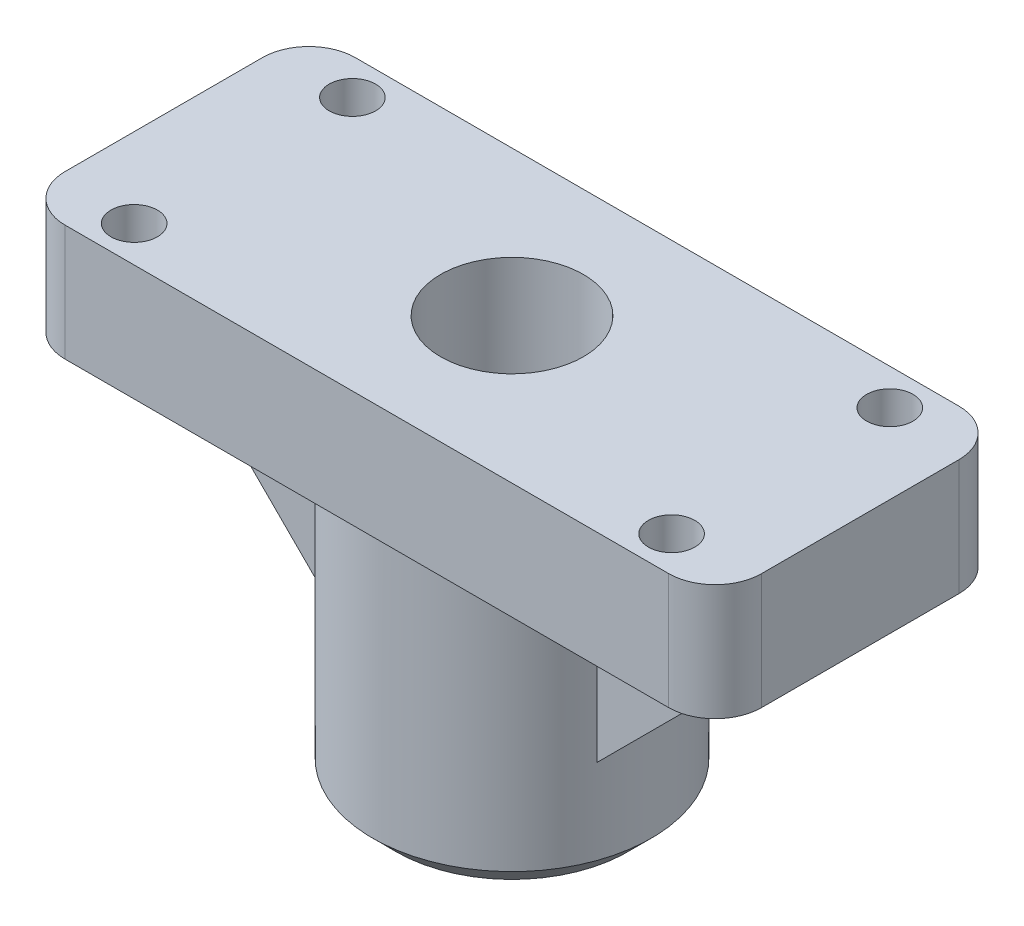
SolidWorks part; units mm, degrees
ref_plane "Front Plane" through (0, 0, 0) normal (0, 0, 1) x (1, 0, 0)
ref_plane "Top Plane" through (0, 0, 0) normal (0, 1, 0) x (1, 0, 0)
ref_plane "Right Plane" through (0, 0, 0) normal (1, 0, 0) x (0, 0, -1)
sketch "Sketch1" plane through (0, 0, 0) normal (0, 1, 0) x (1, 0, 0)
  line L1 (-30, 12.5) -> (30, 12.5)
  line L2 (-30, 12.5) -> (-30, -12.5)
  line L3 (-30, -12.5) -> (30, -12.5)
  line L4 (30, 12.5) -> (30, -12.5)
  point P4 (0, 12.5)
  point P6 (-30, 0)
  dimension "D1" = 25
  dimension "D2" = 60
extrude "Base" add sketch "Sketch1" along normal blind 10
sketch "Sketch2" plane through (0, 0, 0) normal (0, 0, 1) x (1, 0, 0)
  line L0 (0, 0) -> (0, -20.6179) construction
  line L1 (-6.15, 0) -> (-6.15, -7)
  line L2 (-30, 0) -> (30, 0) construction
  line L3 (-6.15, -7) -> (-5.35, -7)
  line L4 (-5.35, -7) -> (-5.35, -25)
  line L5 (-5.35, -25) -> (-12, -25)
  line L6 (-12, -25) -> (-12, 0)
  line L7 (-12, 0) -> (-6.15, 0)
  dimension "D1" = 12
  dimension "D2" = 6.15
  dimension "D3" = 5.35
  dimension "D4" = 25
  dimension "D5" = 7
revolve "Pen Catch" add sketch "Sketch2" angle 360 about L0
sketch "Sketch5" plane through (0, 10, 0) normal (0, 1, 0) x (1, 0, 0)
  circle A0 centre (0, 0) radius 6.15
  dimension "D1" = 12.3
extrude "Pen Hole" cut sketch "Sketch5" against normal up to next
sketch "Sketch4" plane through (0, 0, 0) normal (0, 0, 1) x (1, 0, 0)
  line L0 (-27, 0) -> (-9, 0)
  line L1 (-30, 0) -> (30, 0) construction
  line L2 (-9, 0) -> (-9, -18)
  line L3 (-9, -18) -> (-27, 0)
  line L4 (0, 0) -> (0, -27.3362) construction
  line L5 (-12, 0) -> (-12, -25) construction
  line L6 (9, -18) -> (27, 0)
  line L7 (9, 0) -> (9, -18)
  line L8 (27, 0) -> (9, 0)
  dimension "D1" = 45
  dimension "D2" = 15
  dimension "D3" = 18
extrude "Stab Fins" add sketch "Sketch4" along normal blind 4 and the other way blind 4
fillet "Base Dec" radius 4 4 edges at (-30, 5, -12.5) (30, 5, 12.5) (30, 5, -12.5) (-30, 5, 12.5)
sketch "Sketch8" plane through (0, 10, 0) normal (0, 1, 0) x (1, 0, 0)
  circle A0 centre (23.15, 9.4) radius 2
  circle A1 centre (23.15, -9.4) radius 2
  circle A2 centre (-23.15, 9.4) radius 2
  circle A3 centre (-23.15, -9.4) radius 2
  circle A4 centre (23.15, 9.4) radius 2 construction
  circle A5 centre (23.15, -9.4) radius 2 construction
  circle A6 centre (-23.15, -9.4) radius 2 construction
  circle A7 centre (-23.15, 9.4) radius 2 construction
extrude "Cut-Extrude2" cut sketch "Sketch8" against normal through all
chamfer "Chamfer1" distance 2 angle 45 1 edges at (0, -25, 12)
